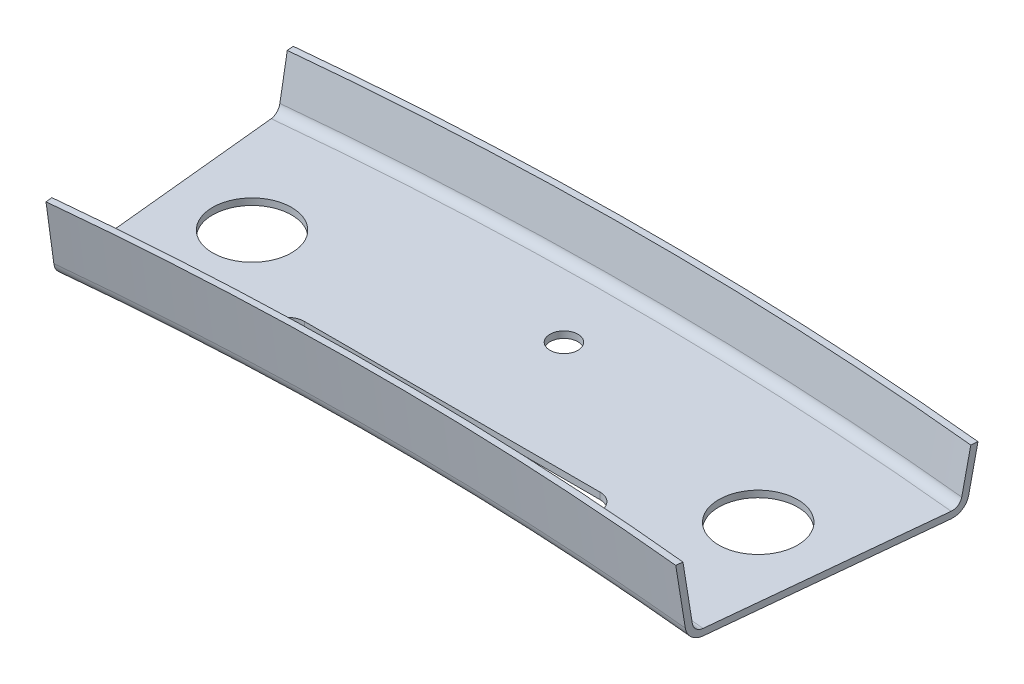
SolidWorks part; units mm, degrees
ref_plane "Front Plane" through (0, 0, 0) normal (0, 0, 1) x (1, 0, 0)
ref_plane "Top Plane" through (0, 0, 0) normal (0, 1, 0) x (1, 0, 0)
ref_plane "Right Plane" through (0, 0, 0) normal (1, 0, 0) x (0, 0, -1)
sketch "Sketch1" plane through (0, 0, 0) normal (0, 1, 0) x (1, 0, 0)
  arc A0 (-100, -5) -> (100, -5) centre (0, -1002.5) cw
  point P3 (0, 0)
  dimension "D1" = 5
  dimension "D2" = 200
sketch "Sketch2" plane through (0, 0, 0) normal (1, 0, 0) x (0, 0, -1)
  line L0 (-34.4785, 0) -> (34.4785, 0)
  line L2 (37.4203, 2.4117) -> (39.9379, 15)
  line L3 (39.9379, 15) -> (41.9379, 15)
  line L4 (41.9379, 15) -> (39.3418, 2.0194)
  line L5 (34.4389, -2) -> (-34.4561, -2)
  line L6 (-39.4008, 2.2583) -> (-42.0621, 20)
  line L7 (-42.0621, 20) -> (-40.0621, 20)
  line L9 (-40.0621, 20) -> (-37.4453, 2.555)
  arc A1 (-34.4785, 0) -> (-37.4453, 2.555) centre (-34.4785, 3) cw
  arc A2 (-34.4561, -2) -> (-39.4008, 2.2583) centre (-34.4561, 3) cw
  arc A3 (39.3418, 2.0194) -> (34.4389, -2) centre (34.4389, 3) cw
  arc A4 (37.4203, 2.4117) -> (34.4785, 0) centre (34.4785, 3) cw
  point P3 (-37.0621, 0)
  point P11 (0, 0)
  point P14 (36.9379, 0)
  point P23 (36.9379, 0)
  dimension "D6" = 3
  dimension "D8" = 3
  dimension "D9" = 5
  dimension "D10" = 5
  dimension "D11" = 3
  dimension "D1" = 17
  dimension "D2" = 80
  dimension "D3" = 3
  dimension "D4" = 2
  dimension "D5" = 2
  dimension "D7" = 22
sweep "Sweep1" add profiles "Sketch2" path "Sketch1"
sketch "Sketch3" plane through (0, 0, 0) normal (0, 1, 0) x (1, 0, 0)
  circle A0 centre (0, 14.9379) radius 4.25
  circle A2 centre (-77, -2.9615) radius 12
  circle A3 centre (77, -2.9615) radius 12
  arc A4 (-77, -2.9615) -> (77, -2.9615) centre (0, -1002.5) cw construction
  arc A5 (95.8043, -46.8523) -> (-95.8043, -46.8523) centre (0, -1002.5) ccw construction
  arc A6 (103.9838, 34.7387) -> (-103.9838, 34.7387) centre (0, -1002.5) ccw construction
  point P8 (0, 39.9379)
  point P12 (0, 0)
  dimension "D1" = 8.5
  dimension "D3" = 24
  dimension "D2" = 25
  dimension "D4" = 154
extrude "Mounting points" cut sketch "Sketch3" against normal through all both and the other way through all
sketch "Sketch4" plane through (0, 0, 0) normal (0, 1, 0) x (1, 0, 0)
  line L0 (-45, -24.0621) -> (45, -24.0621) construction
  line L1 (-45, -19.0621) -> (45, -19.0621)
  line L2 (-45, -29.0621) -> (45, -29.0621)
  arc A0 (-45, -19.0621) -> (-45, -29.0621) centre (-45, -24.0621) ccw
  arc A1 (45, -29.0621) -> (45, -19.0621) centre (45, -24.0621) ccw
  circle A3 centre (0, 14.9379) radius 4.25 construction
  point P2 (0, -24.0621)
  dimension "D1" = 5
  dimension "D2" = 90
  dimension "D3" = 34
extrude "Slot clearance" cut sketch "Sketch4" against normal through all both and the other way through all
sketch "Sketch5" plane through (0, -2, 0) normal (0, -1, 0) x (1, 0, 0)
  line L0 (0, 0) -> (0, 42.0621)
  line L1 (-35, 42.0621) -> (35, 42.0621)
  arc A0 (-95.8043, 46.8523) -> (95.8043, 46.8523) centre (0, 1002.5) ccw construction
  point P8 (0, 42.0621)
  dimension "D1" = 70
ref_plane "Plane1" through (0, 8.6495, 2.3176) normal (0, -0.9659, -0.2588) x (1, 0, 0)
